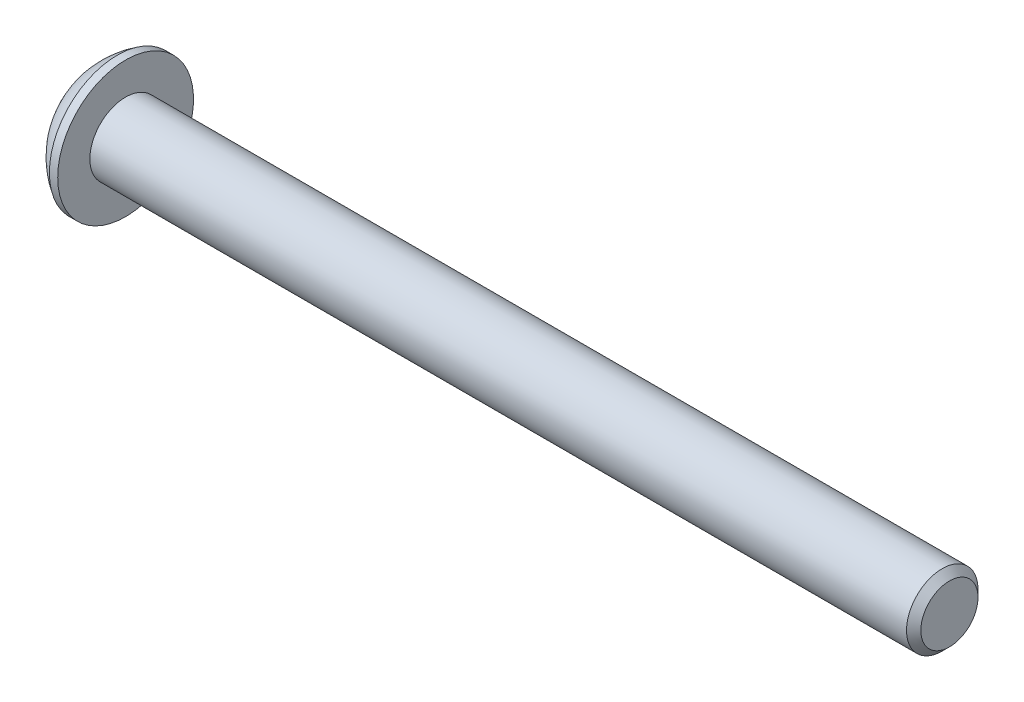
SolidWorks part; units mm, degrees
ref_plane "Plan de face" through (0, 0, 0) normal (0, 0, 1) x (1, 0, 0)
ref_plane "Plan de dessus" through (0, 0, 0) normal (0, 1, 0) x (1, 0, 0)
ref_plane "Plan de droite" through (0, 0, 0) normal (1, 0, 0) x (0, 0, -1)
sketch "Esquisse1" plane through (0, 0, 0) normal (0, 0, 1) x (1, 0, 0)
  line L0 (-65.3427, 0) -> (101.7319, 0) construction
  line L1 (93.1668, 0) -> (93.1668, 1.2)
  line L2 (93.1668, 1.2) -> (92.8668, 1.5)
  line L3 (92.8668, 1.5) -> (58.5868, 1.5)
  line L4 (58.5868, 1.5) -> (58.5868, 2.85)
  line L5 (58.5868, 2.85) -> (58.2368, 2.85)
  line L6 (56.9368, 1.425) -> (56.9368, 0)
  line L7 (58.2368, 2.85) -> (58.2368, 0)
  arc A0 (58.2368, 2.85) -> (56.9368, 1.425) centre (59.9569, -0.0247) ccw
  point P11 (58.5868, 2.175)
  dimension "D6" = 3.35
  dimension "D1" = 1.5
  dimension "D2" = 34.28
  dimension "D3" = 0.35
  dimension "D4" = 0.3
  dimension "D5" = 45
  dimension "D7" = 1.425
  dimension "D8" = 1.65
  dimension "D9" = 2.85
revolve "Révolution1" add sketch "Esquisse1" angle 360 about L0 region at (57.6519, 1.1743, 0) region at (75.5323, 0.7622, 0)
sketch "Esquisse2" plane through (56.9368, 0, 0) normal (-1, 0, 0) x (0, 0, 1)
  line L1 (-1, -0.5774) -> (0, -1.1547)
  line L2 (0, -1.1547) -> (1, -0.5774)
  line L3 (1, -0.5774) -> (1, 0.5774)
  line L4 (1, 0.5774) -> (0, 1.1547)
  line L5 (0, 1.1547) -> (-1, 0.5774)
  line L6 (-1, 0.5774) -> (-1, -0.5774)
  circle A0 centre (0, 0) radius 1.1547 construction
  dimension "D1" = 2
extrude "Enlèv. mat.-Extru.3" cut sketch "Esquisse2" against normal blind 1
